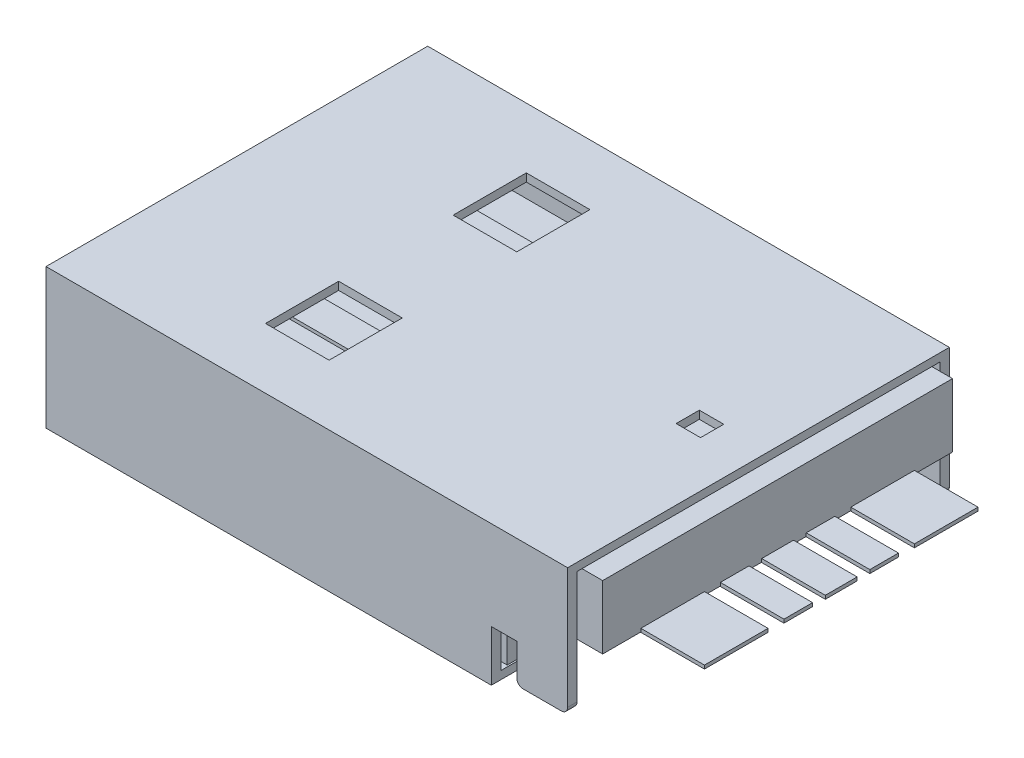
SolidWorks part; units mm, degrees
ref_plane "前视基准面" through (0, 0, 0) normal (0, 0, 1) x (1, 0, 0)
ref_plane "上视基准面" through (0, 0, 0) normal (0, 1, 0) x (1, 0, 0)
ref_plane "右视基准面" through (0, 0, 0) normal (1, 0, 0) x (0, 0, -1)
sketch "草图2" plane through (0, 0, 0) normal (0, 0, 1) x (1, 0, 0)
  line L0 (0, 0) -> (-14, 0)
  line L1 (-14, 0) -> (-14, 2)
  line L2 (-14, 2) -> (-5, 2)
  line L3 (-5, 2) -> (-5, 3.8)
  line L4 (-5, 3.8) -> (3, 3.8)
  line L5 (3, 3.8) -> (3, 1.8)
  line L6 (3, 1.8) -> (0, 1.8)
  line L7 (0, 1.8) -> (0, 0)
  dimension "D1" = 14
  dimension "D2" = 2
  dimension "D3" = 9
  dimension "D4" = 17
  dimension "D5" = 2
  dimension "D6" = 3.8
extrude "凸台-拉伸1" add sketch "草图2" along normal blind 11
sketch "草图3" plane through (0, 2, 0) normal (0, 1, 0) x (1, 0, 0)
  line L0 (-14, -5.5) -> (-5.8182, -5.5) construction
  line L1 (-14, -11) -> (-14, 0) construction
  line L2 (-5, -11) -> (-14, -11) construction
  line L3 (-13, -7) -> (-9, -7)
  line L4 (-13, -7) -> (-13, -6)
  line L5 (-13, -6) -> (-9, -6)
  line L6 (-9, -7) -> (-9, -6)
  line L7 (-13, -9.8) -> (-9, -9.8)
  line L8 (-13, -9.8) -> (-13, -7.8)
  line L9 (-13, -7.8) -> (-9, -7.8)
  line L10 (-9, -9.8) -> (-9, -7.8)
  line L11 (-13, -5) -> (-9, -5)
  line L12 (-9, -4) -> (-9, -5)
  line L13 (-13, -4) -> (-9, -4)
  line L14 (-13, -4) -> (-13, -5)
  line L15 (-13, -3.2) -> (-9, -3.2)
  line L16 (-9, -1.2) -> (-9, -3.2)
  line L17 (-13, -1.2) -> (-9, -1.2)
  line L18 (-13, -1.2) -> (-13, -3.2)
  dimension "D1" = 2
  dimension "D2" = 4
  dimension "D3" = 1
  dimension "D4" = 1
  dimension "D5" = 5
  dimension "D6" = 3.2
extrude "凸台-拉伸2" add sketch "草图3" along normal blind 0.1
ref_plane "基准面1" through (0, 0, 5.5) normal (0, 0, 1) x (1, 0, 0)
sketch "草图5" plane through (0, 2, 0) normal (0, 1, 0) x (1, 0, 0)
  line L0 (-2.2, -5.5) -> (2.2, -5.5) construction
  line L6 (-8.7594, -4.8) -> (-4.0524, -4.8)
  line L7 (-8.7594, -4.8) -> (-8.7594, -6.2)
  line L12 (-8.7594, -6.2) -> (-4.0524, -6.2)
  line L13 (-4.0524, -4.8) -> (-4.0524, -6.2)
  line L14 (-8.7594, -4.8) -> (-4.0524, -6.2) construction
  line L15 (-8.7594, -6.2) -> (-4.0524, -4.8) construction
  point P0 (-6.6179, -5.5)
  point P1 (-6.4059, -5.5)
  point P10 (-6.4059, -5.5)
  dimension "D1" = 1.4
extrude "切除-拉伸2" cut sketch "草图5" against normal through all and the other way through all
sketch "草图4" plane through (0, 0, 5.5) normal (0, 0, 1) x (1, 0, 0)
  line L7 (-8.4864, 0.9775) -> (-7.5448, 2.5523)
  line L8 (-7.5448, 2.5523) -> (-6.9184, 2.5523)
  line L9 (-6.9184, 2.5523) -> (-4.0524, 0.8388)
  line L10 (-4.0524, 0) -> (-4.0524, 3.8) construction
  line L11 (-4.0524, 0.8388) -> (-4.0524, 0.5856)
  line L12 (-4.0524, 0.5856) -> (-6.9238, 2.3024)
  line L13 (-6.9238, 2.3024) -> (-7.4567, 2.3024)
  line L14 (-7.4567, 2.3024) -> (-8.3177, 0.8622)
  line L15 (-8.3177, 0.8622) -> (-8.4864, 0.9775)
extrude "凸台-拉伸3" add sketch "草图4" along normal mid plane 1
fillet "圆角1" radius 0.6 4 edges at (-6.9238, 2.3024, 5.5) (-7.4567, 2.3024, 5.5) (-6.9184, 2.5523, 5.5) (-7.5448, 2.5523, 5.5)
sketch "草图6" plane through (0, 1.8, 0) normal (0, -1, 0) x (1, 0, 0)
  line L0 (0, 5.5) -> (5.3971, 5.5) construction
  line L1 (0, 11) -> (0, 0) construction
  line L2 (5, 4.6) -> (5, 3.7)
  line L3 (0, 7.8) -> (5, 7.8)
  line L4 (0, 7.8) -> (0, 9.8)
  line L5 (0, 9.8) -> (5, 9.8)
  line L6 (5, 7.8) -> (5, 9.8)
  line L7 (0, 6.4) -> (5, 6.4)
  line L8 (0, 6.4) -> (0, 7.3)
  line L9 (0, 7.3) -> (5, 7.3)
  line L10 (5, 6.4) -> (5, 7.3)
  line L11 (0, 3.7) -> (5, 3.7)
  line L12 (0, 4.6) -> (0, 3.7)
  line L13 (0, 4.6) -> (5, 4.6)
  line L14 (5, 3.2) -> (5, 1.2)
  line L15 (0, 1.2) -> (5, 1.2)
  line L16 (0, 3.2) -> (0, 1.2)
  line L17 (0, 3.2) -> (5, 3.2)
  line L18 (0, 11) -> (0, 0) construction
  line L19 (0, 5) -> (5, 5)
  line L20 (0, 5) -> (0, 6)
  line L21 (0, 6) -> (5, 6)
  line L22 (5, 5) -> (5, 6)
  dimension "D1" = 2
  dimension "D2" = 5
  dimension "D3" = 0.9
  dimension "D4" = 8.6
  dimension "D5" = 3.6
  dimension "D6" = 1
extrude "凸台-拉伸4" add sketch "草图6" against normal blind 0.1 and the other way blind 0.01
fillet "圆角2" radius 0.4 1 edges at (-14, 2, 5.5)
sketch "草图8" plane through (-14, 0, 0) normal (-1, 0, 0) x (0, 0, 1)
  line L0 (-0.2, 1.9) -> (-0.5, 1.9) construction
  line L1 (-0.2, -0.05) -> (11.2, -0.05)
  line L2 (-0.2, -0.05) -> (-0.2, 3.85)
  line L3 (-0.2, 3.85) -> (11.2, 3.85)
  line L4 (11.2, -0.05) -> (11.2, 3.85)
  line L5 (-0.5, -0.3) -> (11.5, -0.3)
  line L6 (-0.5, -0.3) -> (-0.5, 4.1)
  line L7 (-0.5, 4.1) -> (11.5, 4.1)
  line L8 (11.5, -0.3) -> (11.5, 4.1)
  line L9 (5.5, 4.1) -> (5.5, 3.8) construction
  line L10 (6.2, 3.8) -> (4.8, 3.8) construction
  line L12 (11, 3.8) -> (6.2, 3.8) construction
  line L13 (11, 0) -> (0, 0) construction
  dimension "D1" = 12
  dimension "D2" = 4.4
  dimension "D3" = 0.05
  dimension "D4" = 0.05
  dimension "D5" = 0.3
  dimension "D6" = 0.3
extrude "凸台-拉伸5" add sketch "草图8" against normal blind 16.4
sketch "草图9" plane through (0, 4.1, 0) normal (0, 1, 0) x (1, 0, 0)
  line L0 (2.4, -5.5) -> (-14, -5.5) construction
  line L1 (2.4, -11.5) -> (2.4, 0.5) construction
  line L2 (-14, -11.5) -> (-14, 0.5) construction
  line L3 (-7, -1.4) -> (-7, -3.7)
  line L4 (-7, -9.6) -> (-9, -9.6)
  line L5 (-7, -9.6) -> (-7, -7.3)
  line L6 (-7, -7.3) -> (-9, -7.3)
  line L7 (-9, -9.6) -> (-9, -7.3)
  line L8 (0.9471, -5.8703) -> (0.1796, -5.8703)
  line L9 (0.9471, -5.8703) -> (0.9471, -5.1405)
  line L10 (0.9471, -5.1405) -> (0.1796, -5.1405)
  line L11 (0.1796, -5.8703) -> (0.1796, -5.1405)
  line L12 (-7, -3.7) -> (-9, -3.7)
  line L13 (-9, -1.4) -> (-9, -3.7)
  line L14 (-7, -1.4) -> (-9, -1.4)
  dimension "D1" = 3.6
  dimension "D2" = 8.2
  dimension "D3" = 2
  dimension "D4" = 5
extrude "切除-拉伸5" cut sketch "草图9" against normal up to next (0.25 mm away)
sketch "草图12" plane through (0, -0.3, 0) normal (0, -1, 0) x (1, 0, 0)
  line L1 (-7, 9.6) -> (-9, 9.6)
  line L2 (-7, 9.6) -> (-7, 7.3)
  line L3 (-7, 7.3) -> (-9, 7.3)
  line L4 (-9, 9.6) -> (-9, 7.3)
  line L5 (-7, 3.7) -> (-9, 3.7)
  line L6 (-7, 3.7) -> (-7, 1.4)
  line L7 (-7, 1.4) -> (-9, 1.4)
  line L8 (-9, 3.7) -> (-9, 1.4)
extrude "切除-拉伸6" cut sketch "草图12" against normal up to next (0.25 mm away)
sketch "草图13" plane through (0, 0, 11.5) normal (0, 0, 1) x (1, 0, 0)
  line L0 (2.4, 0.1) -> (0.8, 0.1)
  line L1 (2.4, -0.05) -> (2.4, 3.85) construction
  line L2 (0.8, 0.1) -> (0.8, 1.3)
  line L3 (0.8, 1.3) -> (0, 1.3)
  line L4 (0, 1.3) -> (0, -0.7818)
  line L5 (0, -0.7818) -> (2.4, -0.7818)
  line L6 (2.4, -0.7818) -> (2.4, 0.1)
  line L7 (2.4, 4.1) -> (-14, 4.1) construction
  line L8 (0, 1.79) -> (0, 1.8) construction
  line L9 (2.4, -0.3) -> (-14, -0.3) construction
  dimension "D1" = 4
  dimension "D2" = 1.6
  dimension "D3" = 1.6
extrude "切除-拉伸7" cut sketch "草图13" against normal through all both and the other way through all
fillet "圆角4" radius 0.2 4 edges at (2.4, 0.1, 11.35) (0.8, 0.1, 11.35) (2.4, 0.1, -0.35) (0.8, 0.1, -0.35)
